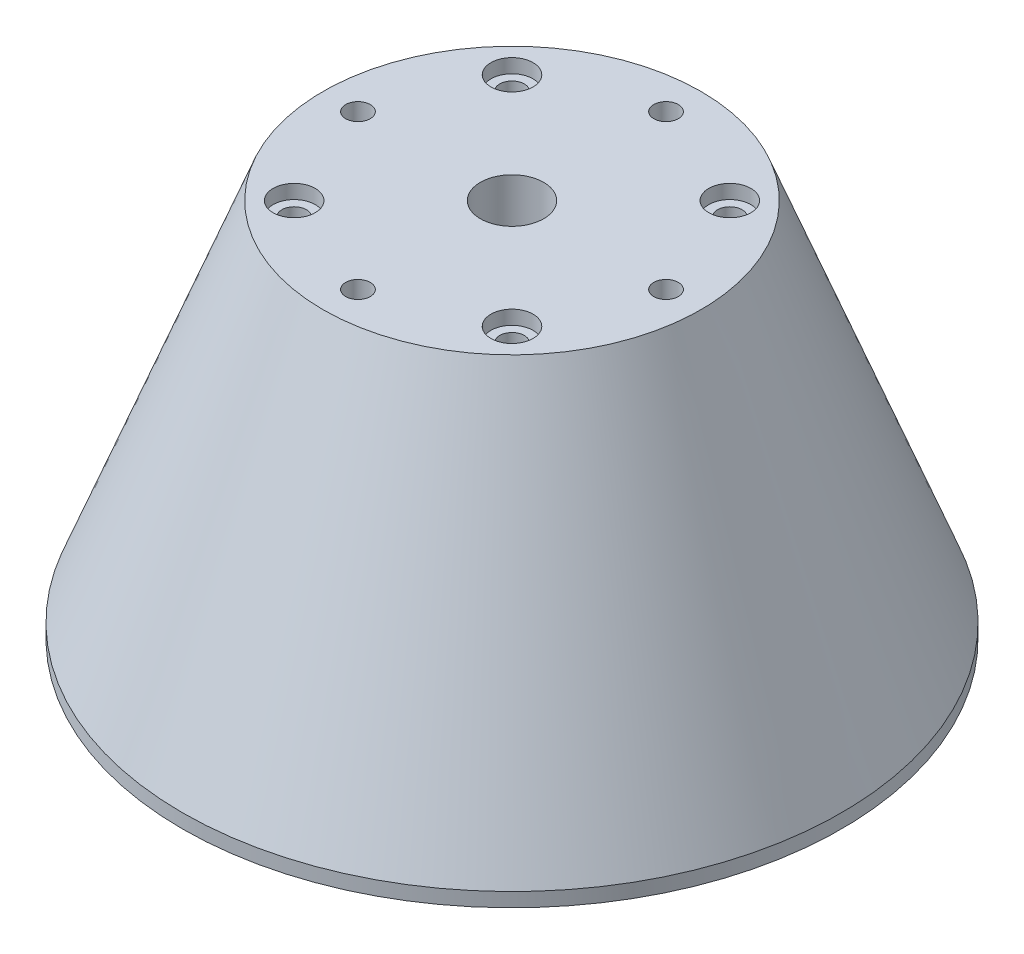
SolidWorks part; units mm, degrees
ref_plane "前视基准面" through (0, 0, 0) normal (0, 0, 1) x (1, 0, 0)
ref_plane "上视基准面" through (0, 0, 0) normal (0, 1, 0) x (1, 0, 0)
ref_plane "右视基准面" through (0, 0, 0) normal (1, 0, 0) x (0, 0, -1)
sketch "草图1" plane through (0, 0, 0) normal (0, 0, 1) x (1, 0, 0)
  line L0 (0, 0) -> (26.9, 0)
  line L6 (43.5538, -52) -> (46.9, -52)
  line L7 (46.9, -52) -> (26.9, 0)
  line L9 (0, 0) -> (0, -12.6)
  line L10 (0, -12.6) -> (26.9, -12.6)
  line L14 (26.9, -12.6) -> (28.4, -12.6)
  line L15 (28.4, -12.6) -> (43.5538, -52)
revolve "旋转1" add sketch "草图1" angle 360 about L9
sketch "草图2" plane through (0, 0, 0) normal (0, 1, 0) x (1, 0, 0)
  line L1 (-15.5, 15.5) -> (15.5, 15.5)
  line L2 (-15.5, 15.5) -> (-15.5, -15.5)
  line L3 (-15.5, -15.5) -> (15.5, -15.5)
  line L4 (15.5, 15.5) -> (15.5, -15.5)
  line L5 (-15.5, 15.5) -> (15.5, -15.5) construction
  line L6 (-15.5, -15.5) -> (15.5, 15.5) construction
  circle A0 centre (15.5, 15.5) radius 1.75
  circle A1 centre (15.5, -15.5) radius 1.75
  circle A2 centre (-15.5, -15.5) radius 1.75
  circle A3 centre (-15.5, 15.5) radius 1.75
  circle A4 centre (0, 21.9203) radius 1.75
  circle A5 centre (15.5, 15.5) radius 1.75
  circle A6 centre (21.9203, 0) radius 1.75
  circle A7 centre (15.5, -15.5) radius 1.75
  circle A8 centre (0, -21.9203) radius 1.75
  circle A9 centre (-15.5, -15.5) radius 1.75
  circle A10 centre (-21.9203, 0) radius 1.75
  point P0 (0, 0)
  point P16 (0, 0)
  point P30 (0, 0)
  dimension "D1" = 4
  dimension "D2" = 8
extrude "切除-拉伸1" cut sketch "草图2" against normal through all contours L1 A3 L2 | L2 A3 L1 | L4 A0 L1 | L1 A0 L4 | L3 A1 L4 | L4 A1 L3 | L2 A2 L3 | L3 A2 L2 | A4 | A10 | A6 | A8 region at (-15.7476, 0, -15.7476) region at (-14.7573, 0, -14.7573) region at (15.7476, 0, -15.7476) region at (14.7573, 0, -14.7573) region at (-14.7573, 0, 14.7573) region at (-15.7476, 0, 15.7476) region at (15.7476, 0, 15.7476) region at (14.7573, 0, 14.7573) region at (0, 0, -21.9203) region at (21.9203, 0, 0) region at (-21.9203, 0, 0)
sketch "草图3" plane through (0, -12.6, 0) normal (0, -1, 0) x (1, 0, 0)
  line L0 (0, -21.9203) -> (-21.9203, 0)
  line L1 (15.5, -15.5) -> (-15.5, -15.5)
  line L2 (15.5, -15.5) -> (15.5, 15.5)
  line L3 (15.5, 15.5) -> (-15.5, 15.5)
  line L4 (-15.5, -15.5) -> (-15.5, 15.5)
  line L5 (15.5, -15.5) -> (-15.5, 15.5) construction
  line L6 (15.5, 15.5) -> (-15.5, -15.5) construction
  line L7 (-15.5, -15.5) -> (-15.5, 15.5)
  line L8 (-21.9203, 0) -> (0, 21.9203)
  line L9 (-15.5, 15.5) -> (15.5, 15.5)
  line L10 (0, 21.9203) -> (21.9203, 0)
  line L11 (15.5, 15.5) -> (15.5, -15.5)
  line L12 (21.9203, 0) -> (0, -21.9203)
  line L13 (-21.9203, 3.2909) -> (-24.7703, 1.6454)
  line L14 (-3.2909, -21.9203) -> (-1.6454, -24.7703)
  line L15 (-1.6454, -24.7703) -> (1.6454, -24.7703)
  line L16 (1.6454, -24.7703) -> (3.2909, -21.9203)
  line L17 (3.2909, -21.9203) -> (1.6454, -19.0703)
  line L18 (1.6454, -19.0703) -> (-1.6454, -19.0703)
  line L19 (-1.6454, -19.0703) -> (-3.2909, -21.9203)
  line L20 (-24.7703, 1.6454) -> (-24.7703, -1.6454)
  line L21 (-24.7703, -1.6454) -> (-21.9203, -3.2909)
  line L22 (-21.9203, -3.2909) -> (-19.0703, -1.6454)
  line L23 (-19.0703, -1.6454) -> (-19.0703, 1.6454)
  line L24 (-19.0703, 1.6454) -> (-21.9203, 3.2909)
  line L25 (3.2909, 21.9203) -> (1.6454, 24.7703)
  line L26 (1.6454, 24.7703) -> (-1.6454, 24.7703)
  line L27 (-1.6454, 24.7703) -> (-3.2909, 21.9203)
  line L28 (-3.2909, 21.9203) -> (-1.6454, 19.0703)
  line L29 (-1.6454, 19.0703) -> (1.6454, 19.0703)
  line L30 (1.6454, 19.0703) -> (3.2909, 21.9203)
  line L31 (21.9203, -3.2909) -> (24.7703, -1.6454)
  line L32 (24.7703, -1.6454) -> (24.7703, 1.6454)
  line L33 (24.7703, 1.6454) -> (21.9203, 3.2909)
  line L34 (21.9203, 3.2909) -> (19.0703, 1.6454)
  line L35 (19.0703, 1.6454) -> (19.0703, -1.6454)
  line L36 (19.0703, -1.6454) -> (21.9203, -3.2909)
  circle A0 centre (0, -21.9203) radius 2.85 construction
  circle A1 centre (-21.9203, 0) radius 2.85 construction
  circle A2 centre (0, 21.9203) radius 2.85 construction
  circle A3 centre (21.9203, 0) radius 2.85 construction
  point P0 (0, 0)
  point P24 (0, 0)
  point P50 (0, 0)
  dimension "D2" = 5.7
  dimension "D1" = 8
  dimension "D3" = 4
extrude "切除-拉伸2" cut sketch "草图3" against normal blind 8 contours L0 L19 L14 L15 L16 L17 L12 | L18 L19 L0 L12 L17 | L12 L36 L31 L32 L33 L34 L10 | L35 L36 L12 L10 L34 | L10 L30 L25 L26 L27 L28 L8 | L29 L30 L10 L8 L28 | L8 L24 L13 L20 L21 L22 L0 | L23 L24 L8 L0 L22 region at (0, -12.6, -22.5435) region at (0, -12.6, -20.1091) region at (-22.5435, -12.6, 0) region at (-20.1091, -12.6, 0) region at (20.1091, -12.6, 0) region at (22.5435, -12.6, 0) region at (0, -12.6, 22.5435) region at (0, -12.6, 20.1091)
sketch "草图4" plane through (0, 0, 0) normal (0, 1, 0) x (1, 0, 0)
  circle A0 centre (-15.5, -15.5) radius 3
  circle A1 centre (-15.5, 15.5) radius 3
  circle A2 centre (15.5, 15.5) radius 3
  circle A3 centre (15.5, -15.5) radius 3
  point P12 (0, 0)
  dimension "D1" = 4
extrude "切除-拉伸3" cut sketch "草图4" against normal blind 2
sketch "草图5" plane through (0, -12.6, 0) normal (0, -1, 0) x (1, 0, 0)
  circle A0 centre (0, 0) radius 11.1
extrude "切除-拉伸4" cut sketch "草图5" against normal blind 2.2
sketch "草图6" plane through (0, -10.4, 0) normal (0, -1, 0) x (1, 0, 0)
  circle A0 centre (0, 0) radius 4.5
extrude "切除-拉伸5" cut sketch "草图6" against normal through all
sketch "草图7" plane through (0, -52, 0) normal (0, -1, 0) x (1, 0, 0)
  circle A0 centre (0, 0) radius 46.9
  circle A1 centre (0, 0) radius 40
extrude "凸台-拉伸1" add sketch "草图7" along normal blind 2
fillet "圆角1" radius 10 1 edges at (0, -52, 43.5538)
